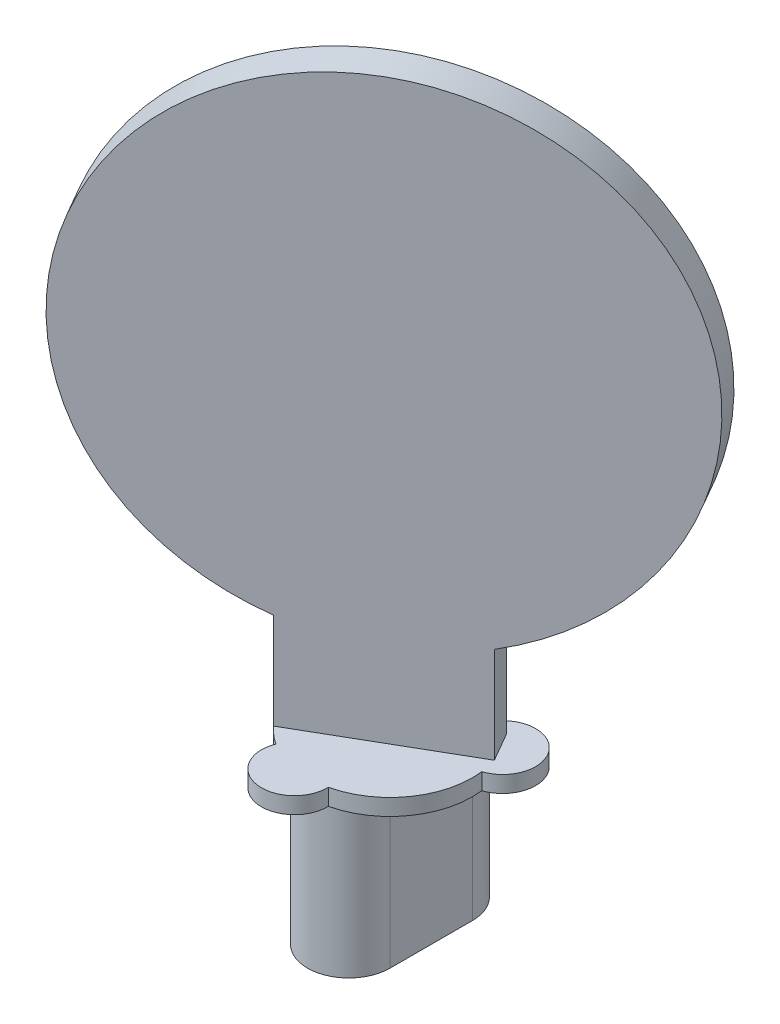
SolidWorks part; units mm, degrees
ref_plane "Front Plane" through (0, 0, 0) normal (0, 0, 1) x (1, 0, 0)
ref_plane "Top Plane" through (0, 0, 0) normal (0, 1, 0) x (1, 0, 0)
ref_plane "Right Plane" through (0, 0, 0) normal (1, 0, 0) x (0, 0, -1)
sketch "Sketch1" plane through (0, 0, 0) normal (0, 1, 0) x (1, 0, 0)
  line L0 (0, 2.5) -> (0, -2.5) construction
  line L1 (2.5, 2.5) -> (2.5, -2.5)
  line L2 (-2.5, 2.5) -> (-2.5, -2.5)
  line L3 (-0.8682, -4.924) -> (-4.6985, 1.7101) construction
  line L4 (3.7426, 3.3155) -> (4.7426, 1.5835)
  line L5 (-1, -4.899) -> (1, -4.899)
  line L6 (-1, -4.899) -> (-1, 4.899)
  line L7 (-1, 4.899) -> (1, 4.899)
  line L8 (1, -4.899) -> (1, 4.899)
  line L9 (-1, -4.899) -> (1, 4.899) construction
  line L10 (-1, 4.899) -> (1, -4.899) construction
  line L11 (3.7426, 3.3155) -> (-4.7426, -1.5835)
  line L12 (4.7426, 1.5835) -> (-3.7426, -3.3155)
  line L13 (-4.7426, -1.5835) -> (-3.7426, -3.3155)
  arc A1 (2.5, 2.5) -> (-2.5, 2.5) centre (0, 2.5) ccw
  arc A2 (-2.5, -2.5) -> (2.5, -2.5) centre (0, -2.5) ccw
  circle A3 centre (4.3301, 2.5) radius 2
  circle A4 centre (-4.6985, 1.7101) radius 2
  circle A5 centre (-0.8682, -4.924) radius 2
  circle A6 centre (0, 0) radius 5
  point P3 (0, 0)
  point P9 (0, 5)
  point P10 (0, -5)
  point P18 (-2.7834, -1.607)
  point P22 (0, 0)
  dimension "D3" = 2.5
  dimension "D4" = 4
  dimension "D5" = 4
  dimension "D6" = 4
  dimension "D7" = 10
  dimension "D2" = 10
  dimension "D9" = 2
  dimension "D10" = 2
  dimension "D1" = 25
  dimension "D8" = 90
  dimension "key_offset_angle" = 60
extrude "Boss-Extrude1" add sketch "Sketch1" against normal blind 10 contours L2 A2 L1 A1
extrude "Boss-Extrude2" add sketch "Sketch1<3>" against normal blind 1 contours A6 A5 | A6 A4 | A6 A3 | A6 region at (4.9993, 0, -2.8864) region at (-1.0024, 0, 5.685) region at (-5.4246, 0, -1.9744)
sketch "Sketch1<3>" plane through (0, 0, 0) normal (0, 1, 0) x (1, 0, 0) same geometry as "Sketch1"
extrude "Boss-Extrude3" add sketch "Sketch1<5>" along normal blind 20 contours L11 L13 L12 L4
sketch "Sketch1<5>" plane through (0, 0, 0) normal (0, 1, 0) x (1, 0, 0) same geometry as "Sketch1"
sketch "Sketch2" plane through (-0.5, 0, -0.866) normal (-0.5, 0, -0.866) x (-0.866, 0, 0.5)
  line L0 (-4.899, 20) -> (4.899, 20) construction
  circle A0 centre (0, 20) radius 15
extrude "Boss-Extrude4" add sketch "Sketch2" against normal blind 2
equation "\"key_pin_length\"= 25.00mm"
equation "\"key_pin_dia\"= 20.00mm"
equation "\"driver_pin_travel\"= 3.00mm"
equation "\"driver_pin_dia\"= 3mm"
equation "\"driver_pin_neck_dia\"= 2.00mm"
equation "\"driver_pin_head_dia\" = 2mm"
equation "\"driver_pin_head_length\" = 2mm"
equation "\"plug_wall_thickness\" = 2mm"
equation "\"plug_spring_solid_length\"= 2mm"
equation "\"plug_length\"= 2 * \"key_pin_length\" + 2 * \"plug_wall_thickness\" + \"plug_spring_solid_length\""
equation "\"plug_dia\"= \"key_pin_dia\" + 2*(\"driver_pin_travel\" + 1mm + \"plug_spring_solid_length\" + 1mm)"
equation "\"true_gate_depth\" = 1.25mm"
equation "\"key_notches_dia\" = 4mm"
equation "\"D4@Sketch1\"=\"key_notches_dia\""
equation "\"D6@Sketch1\"=\"key_notches_dia\""
equation "\"D5@Sketch1\"=\"key_notches_dia\""
equation "\"key_notches_offset_angle\" = 25deg"
equation "\"D1@Sketch1\"=\"key_notches_offset_angle\""
equation "\"key_offset_angle\" = 60deg"
equation "\"key_offset_angle@Sketch1\" = \"key_offset_angle\""
equation "\"key_offset_len\" = 6mm"
equation "\"D1@Boss-Extrude1\"= \"key_offset_len\" + 4mm"
